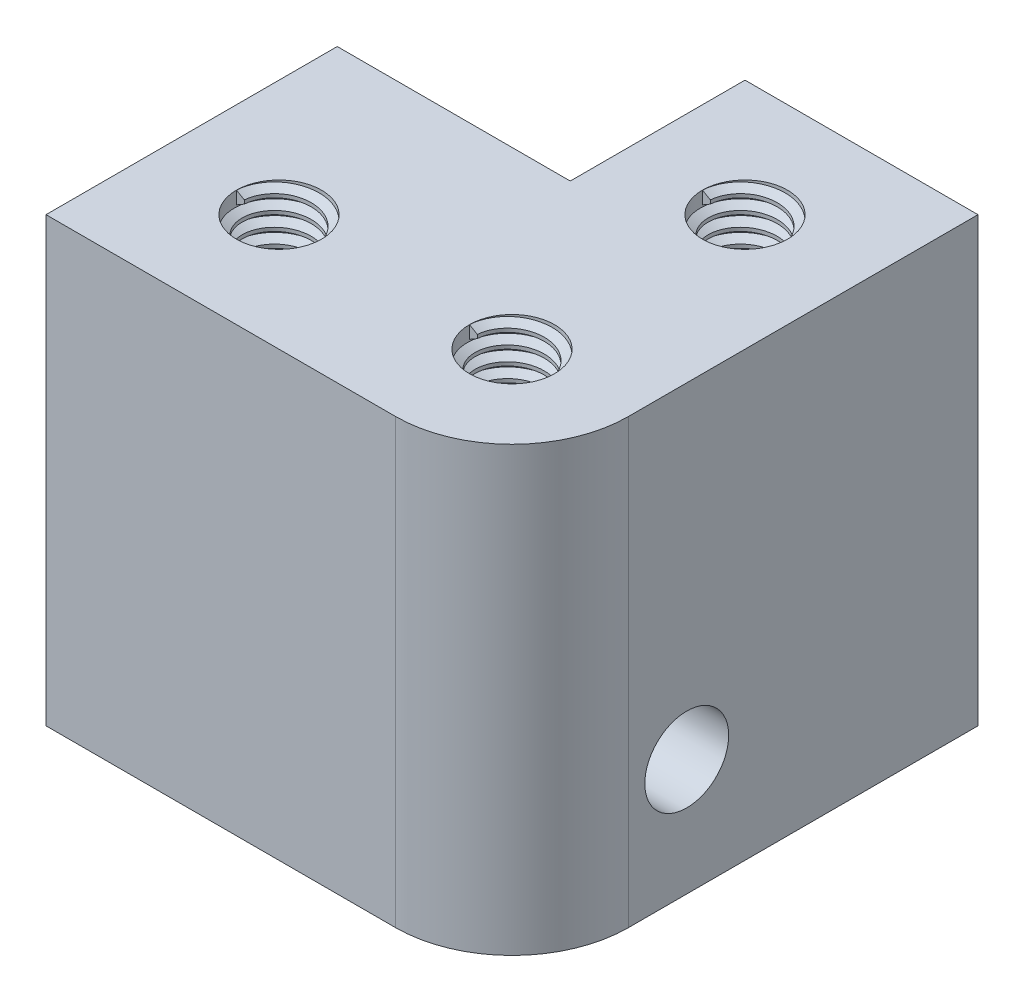
SolidWorks part; units mm, degrees
material "Copper"
ref_plane "Front Plane" through (0, 0, 0) normal (0, 0, 1) x (1, 0, 0)
ref_plane "Top Plane" through (0, 0, 0) normal (0, 1, 0) x (1, 0, 0)
ref_plane "Right Plane" through (0, 0, 0) normal (1, 0, 0) x (0, 0, -1)
sketch "Sketch1" plane through (0, 0, 0) normal (0, 1, 0) x (1, 0, 0)
  line L0 (0, 15.875) -> (12.7, 15.875)
  line L1 (0, 0) -> (19.05, 0)
  line L2 (0, 0) -> (0, 15.875)
  line L3 (12.7, 25.4) -> (25.4, 25.4)
  line L4 (25.4, 6.35) -> (25.4, 25.4)
  line L5 (12.7, 15.875) -> (12.7, 25.4)
  arc A0 (19.05, 0) -> (25.4, 6.35) centre (19.05, 6.35) ccw
  point P7 (25.4, 0)
  point P12 (12.7, 25.4)
  point P15 (12.7, 15.875)
  dimension "D3" = 6.35
  dimension "D1" = 25.4
  dimension "D2" = 25.4
  dimension "D4" = 12.7
  dimension "D5" = 9.525
extrude "Base Extrude" add sketch "Sketch1" along normal blind 24.13
sketch "Sketch2" plane through (25.4, 0, 0) normal (1, 0, 0) x (0, 0, -1)
  line L0 (6.35, 0) -> (25.4, 0) construction
  line L1 (0, 24.13) -> (0, 0) construction
  circle A0 centre (9.525, 6.35) radius 2.286
  dimension "D1" = 4.572
  dimension "D2" = 6.35
  dimension "D3" = 9.525
extrude "Axle Cut" cut sketch "Sketch2" against normal through all
sketch "Sketch3" plane through (0, 24.13, 0) normal (0, 1, 0) x (1, 0, 0)
  line L3 (12.7, 25.4) -> (12.7, 15.875) construction
  line L5 (0, 0) -> (19.05, 0) construction
  circle A0 centre (6.35, 6.35) radius 2.3177
  circle A1 centre (19.05, 6.35) radius 2.3178
  circle A2 centre (19.05, 19.05) radius 2.3178
  dimension "D1" = 4.6355
  dimension "D5" = 6.35
  dimension "D2" = 12.7
  dimension "D3" = 12.7
  dimension "D4" = 6.35
extrude "Mouting Hole Cut" cut sketch "Sketch3" against normal blind 12.7
thread "Front Thread" pitch 0.7937 method extrude profile "Thread Profile1" start angle 0, offset 0, length 12.7, pitch 0.7937, diameter 4.6355
ref_plane "Plane1" through (4.0322, 24.13, -6.35) normal (0, 0, 1) x (-1, 0, 0)
sketch "Thread Profile1" plane through (4.0322, 24.13, -6.35) normal (0, 0, 1) x (-1, 0, 0)
  line L0 (0, 0) -> (0, 0.7937) construction
  line L11 (0, 0) -> (0, 0.6945)
  line L12 (0, 0.6945) -> (-0.4296, 0.4465)
  line L13 (-0.4296, 0.4465) -> (-0.4296, 0.248)
  line L15 (-0.4296, 0.248) -> (0, 0)
  line L17 (-0.4296, 0.3473) -> (0, 0.3473) construction
  point P2 (0, 0)
  dimension "Pitch" = 0.7937
  dimension "Profile_Angle" = 60
  dimension "Profile_Land" = 0.1984
  dimension "Profile_Height" = 0.4296
thread "Middle Thread" pitch 0.7937 method extrude profile "Thread Profile2" start angle 0, offset 0, length 12.7, pitch 0.7937, diameter 4.6355
ref_plane "Plane2" through (16.7322, 24.13, -6.35) normal (0, 0, 1) x (-1, 0, 0)
sketch "Thread Profile2" plane through (16.7322, 24.13, -6.35) normal (0, 0, 1) x (-1, 0, 0)
  line L0 (0, 0) -> (0, 0.7937) construction
  line L11 (0, 0) -> (0, 0.6945)
  line L12 (0, 0.6945) -> (-0.4296, 0.4465)
  line L13 (-0.4296, 0.4465) -> (-0.4296, 0.248)
  line L15 (-0.4296, 0.248) -> (0, 0)
  line L17 (-0.4296, 0.3473) -> (0, 0.3473) construction
  point P2 (0, 0)
  dimension "Pitch" = 0.7937
  dimension "Profile_Angle" = 60
  dimension "Profile_Land" = 0.1984
  dimension "Profile_Height" = 0.4296
thread "Side Thread" pitch 0.7937 method extrude profile "Thread Profile3" start angle 0, offset 0, length 12.7, pitch 0.7937, diameter 4.6355
ref_plane "Plane3" through (16.7322, 24.13, -19.05) normal (0, 0, 1) x (-1, 0, 0)
sketch "Thread Profile3" plane through (16.7322, 24.13, -19.05) normal (0, 0, 1) x (-1, 0, 0)
  line L0 (0, 0) -> (0, 0.7937) construction
  line L11 (0, 0) -> (0, 0.6945)
  line L12 (0, 0.6945) -> (-0.4296, 0.4465)
  line L13 (-0.4296, 0.4465) -> (-0.4296, 0.248)
  line L15 (-0.4296, 0.248) -> (0, 0)
  line L17 (-0.4296, 0.3473) -> (0, 0.3473) construction
  point P2 (0, 0)
  dimension "Pitch" = 0.7937
  dimension "Profile_Angle" = 60
  dimension "Profile_Land" = 0.1984
  dimension "Profile_Height" = 0.4296
